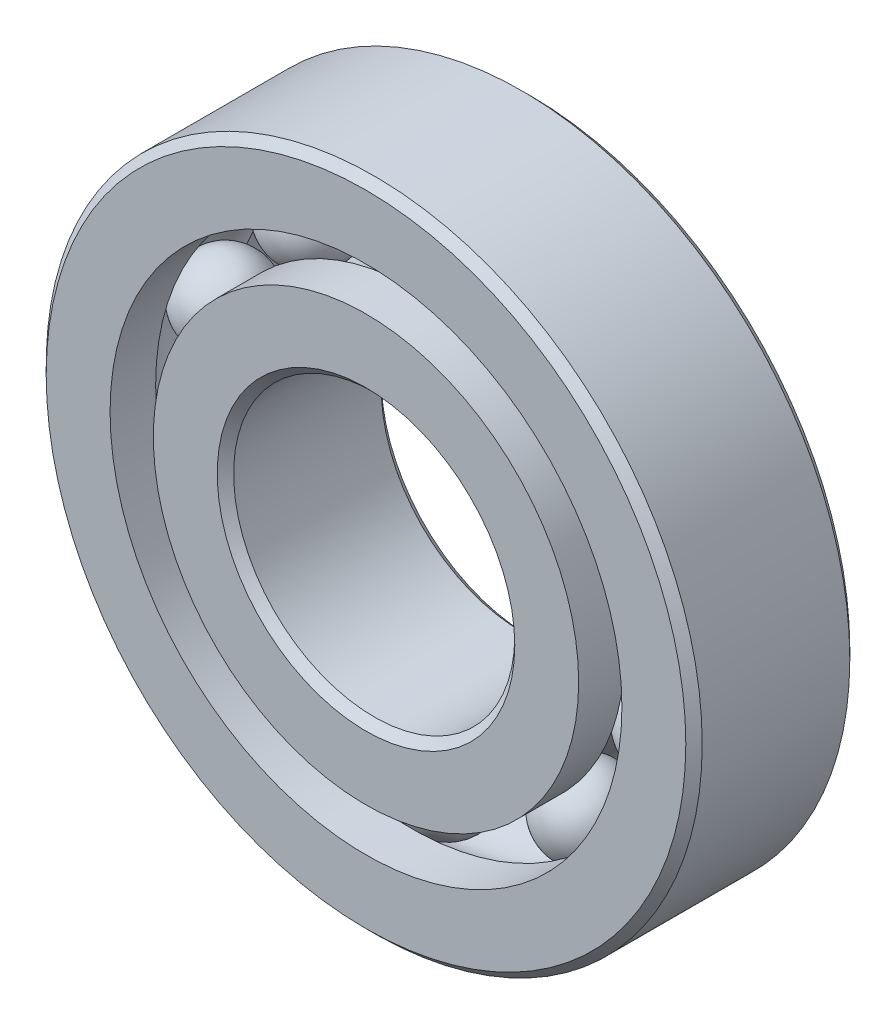
SolidWorks part; units mm, degrees
ref_plane "Front Plane" through (0, 0, 0) normal (0, 0, 1) x (1, 0, 0)
ref_plane "Top Plane" through (0, 0, 0) normal (0, 1, 0) x (1, 0, 0)
ref_plane "Right Plane" through (0, 0, 0) normal (1, 0, 0) x (0, 0, -1)
sketch "Sketch1" plane through (0, 0, 0) normal (1, 0, 0) x (0, 0, -1)
  line L0 (-2.7781, 0) -> (2.7781, 0) construction
  line L1 (0, 11.1125) -> (0, -11.1125) construction
  line L2 (2.5003, 11.1125) -> (-2.5003, 11.1125)
  line L3 (-2.5003, 11.1125) -> (-2.7781, 10.8347)
  line L4 (-2.7781, 10.8347) -> (-2.7781, 8.6702)
  line L5 (-2.7781, 8.6702) -> (-1.2347, 8.6702)
  line L6 (2.7781, 8.6702) -> (1.2347, 8.6702)
  line L7 (2.7781, 10.8347) -> (2.7781, 8.6702)
  line L8 (2.5003, 11.1125) -> (2.7781, 10.8347)
  line L9 (0, 11.1125) -> (0, 7.9375) construction
  line L10 (0, 7.9375) -> (0, 4.7625) construction
  arc A0 (-1.2347, 8.6702) -> (1.2347, 8.6702) centre (0, 7.9375) cw
  point P14 (0, 4.7625)
  dimension "D3" = 2.4694
  dimension "D1" = 45
  dimension "Width" = 5.5562
  dimension "OD" = 22.225
  dimension "D2" = 0.2778
  dimension "Shaft Dia" = 9.525
  dimension "D4" = 0.7327
revolve "Revolve1" add sketch "Sketch1" angle 360 about L0
sketch "Sketch3" plane through (0, 0, 0) normal (1, 0, 0) x (0, 0, -1)
  line L0 (-2.7781, 7.2048) -> (-1.2347, 7.2048)
  line L1 (0, 11.1125) -> (0, -11.1125) construction
  line L2 (-2.7781, 10.8347) -> (-2.7781, 8.6702) construction
  line L3 (-2.7781, 7.2048) -> (-2.7781, 5.0403)
  line L4 (-2.5003, 11.1125) -> (-2.7781, 10.8347) construction
  line L5 (-2.7781, 5.0403) -> (-2.5003, 4.7625)
  line L6 (-2.5003, 4.7625) -> (2.5003, 4.7625)
  line L7 (2.5003, 11.1125) -> (2.5003, -11.1125) construction
  line L8 (2.5003, 4.7625) -> (2.7781, 5.0403)
  line L9 (2.7781, -10.8347) -> (2.7781, 10.8347) construction
  line L10 (2.7781, 5.0403) -> (2.7781, 7.2048)
  line L11 (2.7781, 7.2048) -> (1.2347, 7.2048)
  line L13 (2.5003, 11.1125) -> (2.7781, 10.8347) construction
  arc A0 (1.2347, 8.6702) -> (-1.2347, 8.6702) centre (0, 7.9375) ccw construction
  arc A1 (1.2347, 7.2048) -> (-1.2347, 7.2048) centre (0, 7.9375) cw
revolve "Revolve3" add sketch "Sketch3" angle 360 about L0
sketch "Sketch4" plane through (0, 0, 0) normal (1, 0, 0) x (0, 0, -1)
  line L0 (-1.4357, 7.9375) -> (1.4357, 7.9375)
  arc A2 (-1.4357, 7.9375) -> (1.4357, 7.9375) centre (0, 7.9375) cw
  arc A3 (1.2347, 8.6702) -> (-1.2347, 8.6702) centre (0, 7.9375) ccw construction
revolve "Revolve4" add sketch "Sketch4" angle 360 about L0
ref_axis "Axis1" through (0, 0, -2.7781) along (0, 0, 1)
pattern_circular "CirPattern1" count 10 every 36 about axis through (0, 0, -2.7781) along (0, 0, 1) of bodies 104
equation "\"D2@Sketch1\" = \"Width@Sketch1\"*.05"
equation "\"D3@Sketch1\" = \"Width@Sketch1\"/2.25"
equation "\"D4@Sketch1\" = (((\"OD@Sketch1\"-\"Width@Sketch1\")/2)/3.25)/3.5"
equation "\"D2@CirPattern1\" = 360/\"Balls@CirPattern1\""
